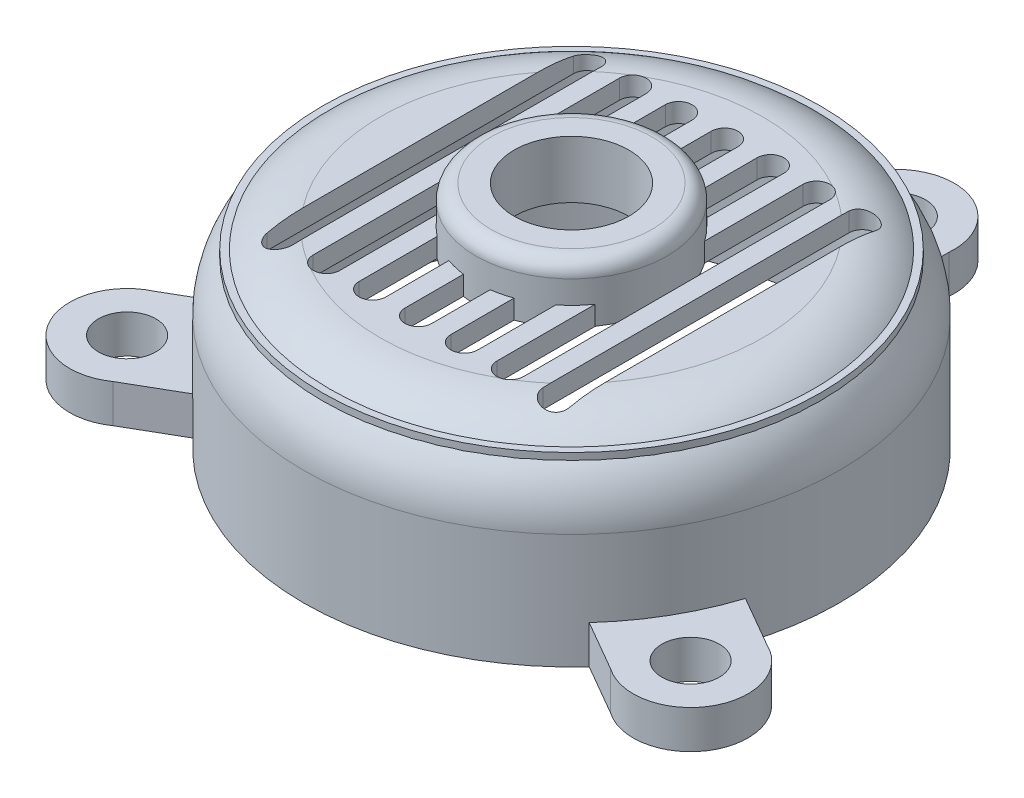
SolidWorks part; units mm, degrees
ref_plane "Front Plane" through (0, 0, 0) normal (0, 0, 1) x (1, 0, 0)
ref_plane "Top Plane" through (0, 0, 0) normal (0, 1, 0) x (1, 0, 0)
ref_plane "Right Plane" through (0, 0, 0) normal (1, 0, 0) x (0, 0, -1)
sketch "Sketch1" plane through (0, 0, 0) normal (0, 1, 0) x (1, 0, 0)
  line L0 (0, 0) -> (0, 4.6838) construction
  line L1 (0.7471, 3.4193) -> (0.7471, 4.1838)
  line L2 (-0.7471, 4.1838) -> (-0.7471, 3.4193)
  line L3 (2.5877, -2.3567) -> (3.2498, -2.7389)
  line L4 (3.9968, -1.4449) -> (3.3348, -1.0627)
  line L5 (-3.3348, -1.0627) -> (-3.9968, -1.4449)
  line L6 (-3.2498, -2.7389) -> (-2.5877, -2.3567)
  circle A0 centre (0, 0) radius 3.5
  circle A1 centre (0, 0) radius 3.25
  circle A2 centre (0, 0) radius 4.25 construction
  arc A3 (0.7471, 4.1838) -> (-0.7471, 4.1838) centre (0, 4.25) ccw
  circle A4 centre (0, 4.25) radius 0.375
  arc A5 (3.2498, -2.7389) -> (3.9968, -1.4449) centre (3.6806, -2.125) ccw
  circle A6 centre (3.6806, -2.125) radius 0.375
  arc A7 (-3.9968, -1.4449) -> (-3.2498, -2.7389) centre (-3.6806, -2.125) ccw
  circle A8 centre (-3.6806, -2.125) radius 0.375
  point P12 (0, 0)
  point P13 (0, 0)
  point P14 (-2.7043, -2.5587)
  point P27 (0, 0)
  point P28 (0, 0)
  dimension "D1" = 7
  dimension "D2" = 0.25
  dimension "D3" = 8.5
  dimension "D4" = 0.75
  dimension "D5" = 0.75
  dimension "D6" = 3
extrude "Boss-Extrude1" add sketch "Sketch1" along normal blind 2.5 contours A0
shell "Shell1" thickness 0.25 removed face at (0, 0, 3.5)
extrude "Boss-Extrude2" add sketch "Sketch1<3>" along normal blind 0.5 contours L3 A5 L4 A0 A6 | L1 A3 L2 A0 A4 | L5 A7 L6 A0 A8 region at (0, 0, -3.5218) region at (3.6529, 0, 1.2762) region at (-3.0535, 0, 1.7629)
sketch "Sketch1<3>" plane through (0, 0, 0) normal (0, 1, 0) x (1, 0, 0) same geometry as "Sketch1"
sketch "Sketch3" plane through (0, 2.5, 0) normal (0, 1, 0) x (1, 0, 0)
  line L0 (0, 0) -> (0, 2.9445) construction
  line L1 (0, 0) -> (3.5, 0) construction
  line L2 (1.8, -2) -> (1.8, 2) construction
  line L3 (1.975, -2) -> (1.975, 2)
  line L4 (1.625, -2) -> (1.625, 2)
  circle A0 centre (0, 0) radius 3.5 construction
  arc A1 (1.625, 2) -> (1.975, 2) centre (1.8, 2) cw
  arc A2 (1.625, -2) -> (1.975, -2) centre (1.8, -2) ccw
  point P10 (1.8, 0)
  dimension "D1" = 1.8
  dimension "D2" = 4
  dimension "D3" = 0.175
  dimension "D4" = 0.175
fillet "Fillet2" radius 1 1 edges at (0, 2.5, 3.5)
extrude "Cut-Extrude1" cut sketch "Sketch3" against normal through all both and the other way through all contours L4 A2 L3 A1 region at (1.8, 2.5, 0)
pattern_linear "LPattern3" count 7 spacing 0.6 along (-1, 0, 0) of "Cut-Extrude1"
sketch "Sketch4" plane through (0, 2.5, 0) normal (0, 1, 0) x (1, 0, 0)
  circle A0 centre (0, 0) radius 1.25
  circle A1 centre (0, 0) radius 0.75
  dimension "D1" = 2.5
  dimension "D2" = 1.5
extrude "Boss-Extrude3" add sketch "Sketch4" along normal blind 0.75 from surface starting at face at (0.6, 2.25, 0)
fillet "Fillet3" radius 0.2 1 edges at (0, 3, 1.25)
extrude "Cut-Extrude2" cut sketch "Sketch4<2>" against normal through all both contours A1
sketch "Sketch4<2>" plane through (0, 2.5, 0) normal (0, 1, 0) x (1, 0, 0) same geometry as "Sketch4"
